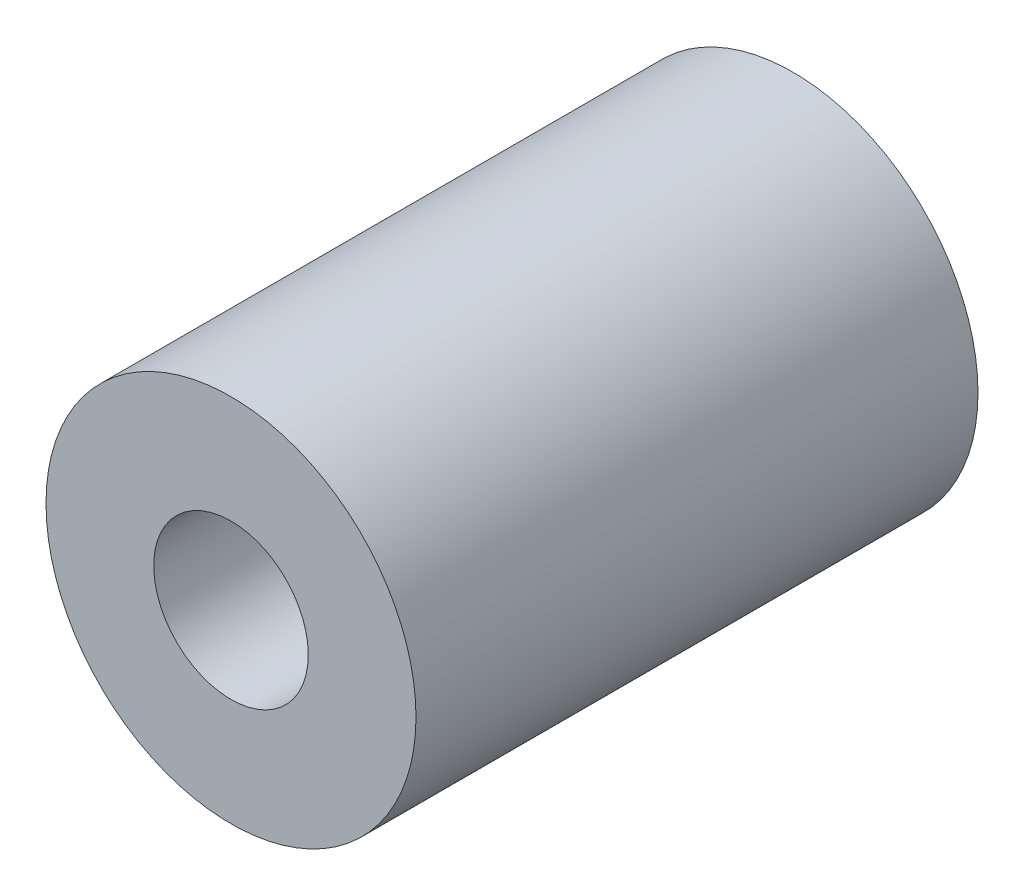
SolidWorks part; units mm, degrees
ref_plane "Front Plane" through (0, 0, 0) normal (0, 0, 1) x (1, 0, 0)
ref_plane "Top Plane" through (0, 0, 0) normal (0, 1, 0) x (1, 0, 0)
ref_plane "Right Plane" through (0, 0, 0) normal (1, 0, 0) x (0, 0, -1)
sketch "Sketch1" plane through (0, 0, 0) normal (0, 0, 1) x (1, 0, 0)
  circle A0 centre (0, 0) radius 3.95
  circle A1 centre (0, 0) radius 1.65
  dimension "D1" = 7.9
  dimension "D2" = 3.3
extrude "Boss-Extrude1" add sketch "Sketch1" along normal mid plane 12
